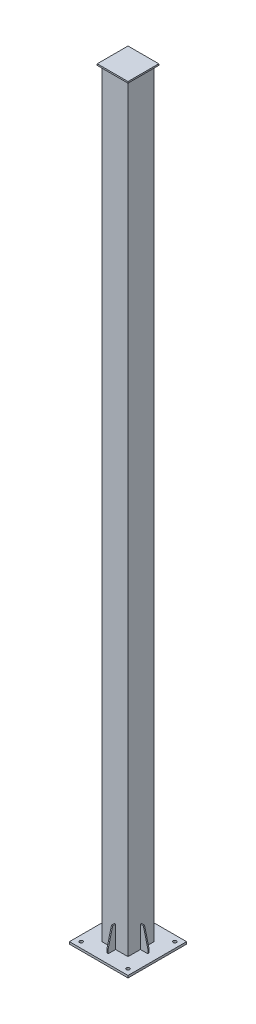
SolidWorks part; units mm, degrees
material "Gray Cast Iron"
ref_plane "Front Plane" through (0, 0, 0) normal (0, 0, 1) x (1, 0, 0)
ref_plane "Top Plane" through (0, 0, 0) normal (0, 1, 0) x (1, 0, 0)
ref_plane "Right Plane" through (0, 0, 0) normal (1, 0, 0) x (0, 0, -1)
sketch "Sketch1" plane through (0, 0, 0) normal (0, -1, 0) x (1, 0, 0)
  line L0 (-83.9, 83.9) -> (-83.9, -83.9)
  line L1 (-88.9, 88.9) -> (88.9, 88.9)
  line L2 (-88.9, 88.9) -> (-88.9, -88.9)
  line L3 (-88.9, -88.9) -> (88.9, -88.9)
  line L4 (88.9, 88.9) -> (88.9, -88.9)
  line L5 (-88.9, 88.9) -> (88.9, -88.9) construction
  line L6 (-88.9, -88.9) -> (88.9, 88.9) construction
  line L7 (-83.9, -83.9) -> (83.9, -83.9)
  line L8 (83.9, 83.9) -> (83.9, -83.9)
  line L9 (-83.9, 83.9) -> (83.9, 83.9)
  point P0 (0, 0)
  dimension "D1" = 177.8
  dimension "D2" = 5
extrude "Boss-Extrude1" add sketch "Sketch1" along normal blind 5181.6
sketch "Sketch4" plane through (0, 0, 0) normal (0, 1, 0) x (1, 0, 0)
  line L3 (-105, 105) -> (105, 105)
  line L4 (-105, 105) -> (-105, -105)
  line L5 (-105, -105) -> (105, -105)
  line L6 (105, 105) -> (105, -105)
  line L7 (-105, 105) -> (105, -105) construction
  line L8 (-105, -105) -> (105, 105) construction
  point P5 (0, 0)
  dimension "D1" = 210
  dimension "D2" = 210
extrude "Boss-Extrude3" add sketch "Sketch4" along normal blind 10
ref_plane "Plane1" through (0, -3048, 0) normal (0, 1, 0) x (1, 0, 0)
sketch "Sketch5" plane through (0, 10, 0) normal (0, 1, 0) x (1, 0, 0)
  line L0 (0, 105) -> (0, -105) construction
  line L1 (105, 105) -> (-105, 105) construction
  line L2 (-105, -105) -> (105, -105) construction
  line L3 (-105, 0) -> (105, 0) construction
  line L4 (-105, 105) -> (-105, -105) construction
  line L5 (105, -105) -> (105, 105) construction
sketch "Sketch6" plane through (0, -5181.6, 0) normal (0, -1, 0) x (1, 0, 0)
  line L3 (-200, 200) -> (200, 200)
  line L4 (-200, 200) -> (-200, -200)
  line L5 (-200, -200) -> (200, -200)
  line L6 (200, 200) -> (200, -200)
  line L7 (-200, 200) -> (200, -200) construction
  line L8 (-200, -200) -> (200, 200) construction
  circle A0 centre (-160, 160) radius 11
  circle A1 centre (160, 160) radius 11
  circle A2 centre (160, -160) radius 11
  circle A3 centre (-160, -160) radius 11
  circle A4 centre (0, 0) radius 10
  point P5 (0, 0)
  point P17 (0, 0)
  dimension "D3" = 22
  dimension "D6" = 20
  dimension "D1" = 400
  dimension "D2" = 400
  dimension "D4" = 40
  dimension "D5" = 4
extrude "Boss-Extrude4" add sketch "Sketch6" along normal blind 15
sketch "Sketch7" plane through (0, 0, 0) normal (1, 0, 0) x (0, 0, -1)
  line L0 (88.9, -5031.6) -> (108.9, -5031.6)
  line L1 (88.9, -5181.6) -> (88.9, 0) construction
  line L2 (108.9, -5031.6) -> (138.9, -5151.6)
  line L3 (138.9, -5151.6) -> (138.9, -5181.6)
  line L4 (200, -5181.6) -> (-200, -5181.6) construction
  line L5 (138.9, -5181.6) -> (88.9, -5181.6)
  line L6 (88.9, -5181.6) -> (88.9, -5031.6)
  dimension "D1" = 20
  dimension "D2" = 150
  dimension "D3" = 50
  dimension "D4" = 30
extrude "Boss-Extrude5" add sketch "Sketch7" along normal mid plane 8 separate body
ref_axis "Axis1" through (0, 214.45, 0) along (0, -1, 0)
pattern_circular "CirPattern1" count 4 over 360 about axis through (0, 214.45, 0) along (0, -1, 0) of bodies 110
